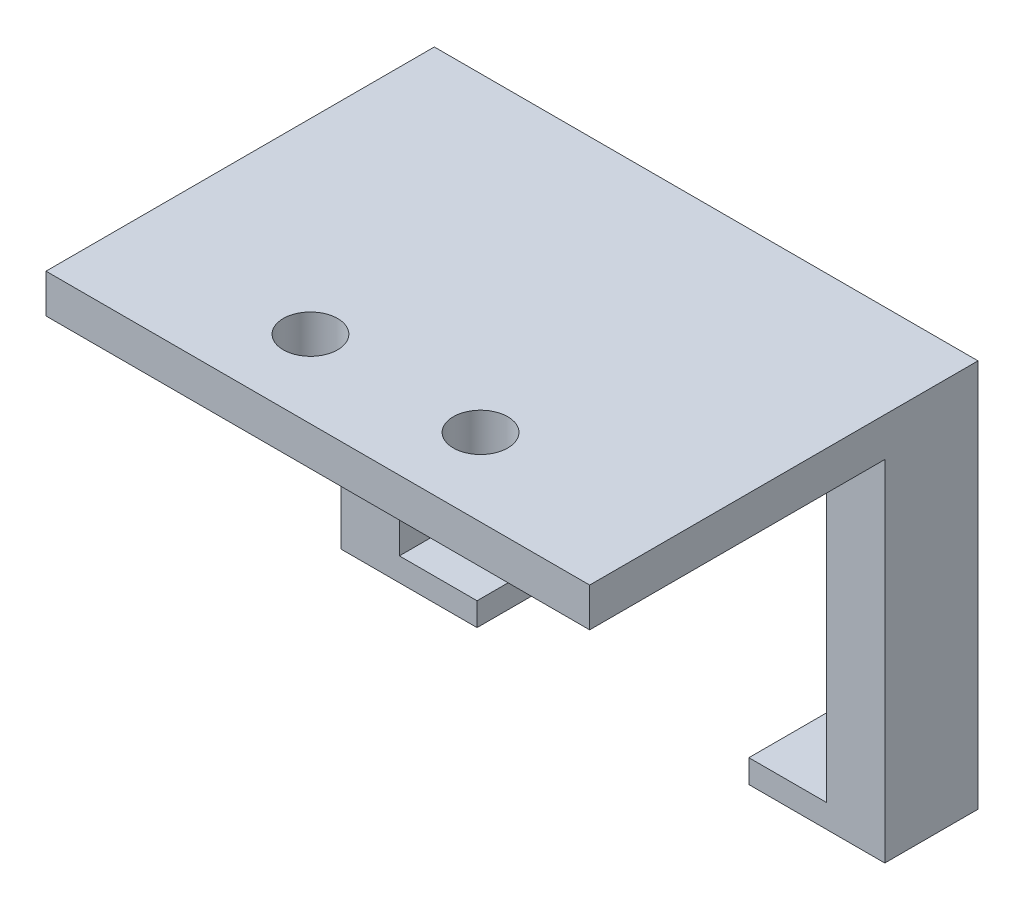
SolidWorks part; units mm, degrees
material "Custom Plastic"
ref_plane "Front Plane" through (0, 0, 0) normal (0, 0, 1) x (1, 0, 0)
ref_plane "Top Plane" through (0, 0, 0) normal (0, 1, 0) x (1, 0, 0)
ref_plane "Right Plane" through (0, 0, 0) normal (1, 0, 0) x (0, 0, -1)
sketch "Sketch3" plane through (0, 0, 0) normal (0, 1, 0) x (1, 0, 0)
  line L1 (-11.5173, 12.4673) -> (24.0427, 12.4673)
  line L2 (-11.5173, 12.4673) -> (-11.5173, -12.9327)
  line L3 (-11.5173, -12.9327) -> (24.0427, -12.9327)
  line L4 (24.0427, 12.4673) -> (24.0427, -12.9327)
  circle A0 centre (0.7001, -7.8527) radius 1.778
  circle A2 centre (11.8253, -7.8527) radius 1.778
  dimension "D2" = 3.556
  dimension "D3" = 3.556
  dimension "D1" = 25.4
  dimension "1" = 35.56
  dimension "D4" = 11.1252
  dimension "D5" = 12.2174
  dimension "D6" = 20.32
extrude "Boss-Extrude3" add sketch "Sketch3" along normal blind 2.54
sketch "Sketch4" plane through (0, 0, 0) normal (0, -1, 0) x (1, 0, 0)
  line L0 (-11.5173, -12.4673) -> (-11.5173, 12.9327) construction
  line L1 (-11.5173, -1.2913) -> (-7.7073, -1.2913)
  line L2 (-11.5173, -1.2913) -> (-11.5173, -12.4673)
  line L3 (-11.5173, -12.4673) -> (-7.7073, -12.4673)
  line L4 (-7.7073, -1.2913) -> (-7.7073, -12.4673)
  line L5 (24.0427, -12.4673) -> (-11.5173, -12.4673) construction
  line L6 (-11.5173, 12.9327) -> (24.0427, 12.9327) construction
  line L7 (24.0427, 12.9327) -> (24.0427, -12.4673) construction
  line L8 (24.0427, -1.2913) -> (20.2327, -1.2913)
  line L9 (24.0427, -1.2913) -> (24.0427, -12.4673)
  line L10 (24.0427, -12.4673) -> (20.2327, -12.4673)
  line L11 (20.2327, -1.2913) -> (20.2327, -12.4673)
  dimension "D1" = 14.224
  dimension "D2" = 3.81
  dimension "D3" = 14.224
  dimension "D4" = 3.81
extrude "Boss-Extrude4" add sketch "Sketch4" along normal blind 22.86
sketch "Sketch5" plane through (-7.7073, 0, 0) normal (1, 0, 0) x (0, 0, -1)
  line L0 (1.2913, -22.86) -> (1.2913, 0) construction
  line L1 (1.2913, -21.336) -> (12.4673, -21.336)
  line L2 (1.2913, -21.336) -> (1.2913, -22.86)
  line L3 (1.2913, -22.86) -> (12.4673, -22.86)
  line L4 (12.4673, -21.336) -> (12.4673, -22.86)
  dimension "D1" = 1.524
extrude "Boss-Extrude5" add sketch "Sketch5" along normal blind 5.08
sketch "Sketch6" plane through (20.2327, 0, 0) normal (-1, 0, 0) x (0, 0, 1)
  line L0 (-12.4673, 2.54) -> (-12.4673, -22.86) construction
  line L1 (-12.4673, -21.336) -> (-1.2913, -21.336)
  line L2 (-12.4673, -21.336) -> (-12.4673, -22.86)
  line L3 (-12.4673, -22.86) -> (-1.2913, -22.86)
  line L4 (-1.2913, -21.336) -> (-1.2913, -22.86)
  dimension "D1" = 1.524
extrude "Boss-Extrude6" add sketch "Sketch6" along normal blind 5.08
sketch "Sketch7" plane through (0, 0, -1.2913) normal (0, 0, 1) x (1, 0, 0)
  line L1 (-11.5173, 0) -> (24.0427, 0)
  line L2 (-11.5173, 0) -> (-11.5173, -22.86)
  line L3 (-11.5173, -22.86) -> (24.0427, -22.86)
  line L4 (24.0427, 0) -> (24.0427, -22.86)
extrude "Cut-Extrude1" cut sketch "Sketch7" against normal blind 5.08
